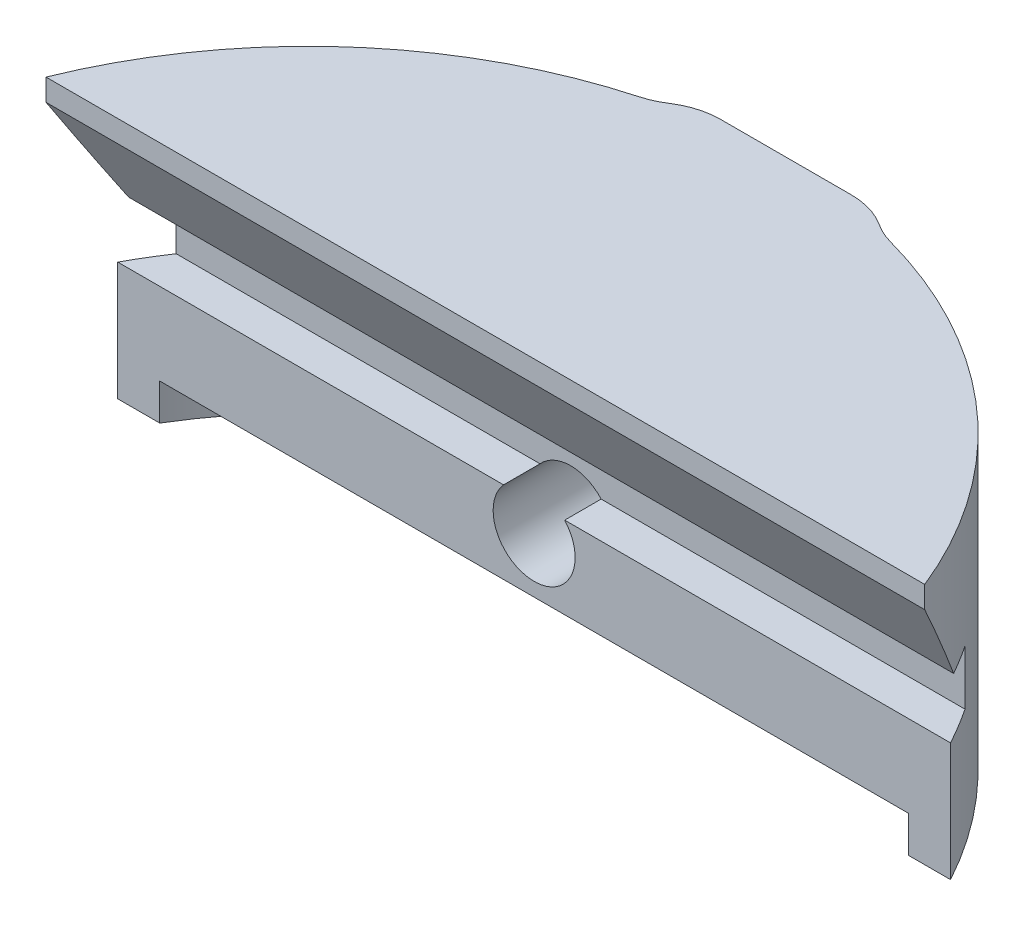
SolidWorks part; units mm, degrees
material "3.1355 (EN-AW 2024)"
ref_plane "Спереди" through (0, 0, 0) normal (0, 0, 1) x (1, 0, 0)
ref_plane "Сверху" through (0, 0, 0) normal (0, 1, 0) x (1, 0, 0)
ref_plane "Справа" through (0, 0, 0) normal (1, 0, 0) x (0, 0, -1)
sketch "Эскиз1" plane through (0, 0, 0) normal (0, 1, 0) x (1, 0, 0)
  circle A0 centre (0, 0) radius 26
  dimension "D1" = 52
extrude "Бобышка-Вытянуть1" add sketch "Эскиз1" along normal blind 14
sketch "Эскиз2" plane through (0, 0, 0) normal (1, 0, 0) x (0, 0, -1)
  line L0 (0, 14) -> (0, 0) construction
  line L1 (26, 14) -> (-26, 14) construction
  line L2 (13.6547, 6) -> (-13.6547, 6)
  line L3 (-13.6547, 6) -> (-9.7287, 12.8)
  line L4 (-9.7287, 12.8) -> (-9.7287, 14)
  line L5 (-9.7287, 14) -> (9.7287, 14)
  line L6 (0, 14) -> (0, 6) construction
  line L7 (13.6547, 6) -> (9.7287, 12.8)
  line L8 (9.7287, 12.8) -> (9.7287, 14)
  line L9 (-12.5, 8) -> (-12.5, 6) construction
  dimension "D1" = 8
  dimension "D2" = 1.2
  dimension "D3" = 60
  dimension "D4" = 13.6547
  dimension "D5" = 9.7287
  dimension "D6" = 2
  dimension "D7" = 12.5
extrude "Вырез-Вытянуть1" cut sketch "Эскиз2" against normal mid plane 60
sketch "Примерка" plane through (0, 0, 0) normal (1, 0, 0) x (0, 0, -1)
  line L0 (13.6547, 6) -> (-13.6547, 6) construction
  line L1 (-12.5, 14) -> (12.5, 14)
  line L2 (-12.5, 14) -> (-12.5, 6)
  line L3 (-12.5, 6) -> (12.5, 6)
  line L4 (12.5, 14) -> (12.5, 6)
  point P6 (0, 6)
  dimension "D1" = 8
  dimension "D2" = 25
sketch "Эскиз5" plane through (0, 0, 0) normal (0, -1, 0) x (1, 0, 0)
  line L2 (-22.1258, -15.6547) -> (22.1258, -15.6547)
  line L3 (-18.1915, -15.6547) -> (18.1915, -15.6547)
  circle A2 centre (0, 0) radius 24
  arc A3 (-18.1915, -15.6547) -> (18.1915, -15.6547) centre (0, 0) ccw
  dimension "D1" = 2
  dimension "D2" = 2
sketch "Эскиз6" plane through (0, 6, 0) normal (0, 1, 0) x (1, 0, 0)
  line L1 (18.4208, 0) -> (-15.4735, 0) construction
  circle A0 centre (0, 0) radius 6 construction
  circle A1 centre (0, 0) radius 12.5 construction
  dimension "D1" = 12
  dimension "D2" = 25
hole_wizard "Цековка для винта с внутренним шестигранником M32" positions "Эскиз14" profile "Эскиз13" counterbore size "M3" standard "Ansi Metric" end condition up to next
sketch "Эскиз14" plane through (0, 6, 0) normal (0, 1, 0) x (1, 0, 0)
  line L0 (18.4208, 0) -> (-15.4735, 0) construction
  circle A0 centre (0, 0) radius 12.5 construction
  circle A1 centre (0, 0) radius 6 construction
  point P0 (-12.5, 0)
  point P6 (12.5, 0)
  point P20 (-6, 0)
  point P24 (6, 0)
sketch "Эскиз13" plane through (-12.5, 6, 0) normal (1, 0, 0) x (0, 0, 1)
  line L0 (0, 0) -> (0, 6)
  line L1 (0, 6) -> (1.7, 6)
  line L3 (1.7, 6) -> (1.7, 3)
  line L4 (1.7, 3) -> (3.3, 3)
  line L5 (3.3, 3) -> (3.3, 0)
  line L7 (3.3, 0) -> (0, 0)
  line L11 (0, -6.35) -> (0, 107.95) construction
  dimension "Диаметр сквозного отверстия" = 3.4
  dimension "Глубина сквозного отверстия" = 6
  dimension "Диаметр цековки" = 6.6
  dimension "Глубина цековки" = 3
sketch "Эскиз12" plane through (0, 0, 0) normal (0, -1, 0) x (1, 0, 0)
  circle A0 centre (0, 0) radius 26 construction
  circle A1 centre (0, 0) radius 26
  circle A3 centre (0, 0) radius 24
  dimension "D1" = 2
extrude "Бобышка-Вытянуть2" add sketch "Эскиз12" along normal blind 2
sketch "Эскиз17" plane through (0, 14, 0) normal (0, 1, 0) x (1, 0, 0)
  line L0 (-24.1112, -9.7287) -> (24.1112, -9.7287) construction
  line L1 (-24.1112, -9.7287) -> (24.1112, -9.7287)
  arc A0 (-24.1112, -9.7287) -> (24.1112, -9.7287) centre (0, 0) ccw construction
  arc A1 (-24.1112, -9.7287) -> (24.1112, -9.7287) centre (0, 0) ccw
extrude "Вырез-Вытянуть4" cut sketch "Эскиз17" against normal up to surface (8 mm away) up to face at (9.25, 6, 0)
fillet "Скругление2" radius 1 4 edges at (9.25, 4.5, -0.5723) (9.25, 4.5, 0.5723) (-9.25, 4.5, 0.5723) (-9.25, 4.5, -0.5723)
sketch "Эскиз18" plane through (0, 0, 0) normal (0, -1, 0) x (1, 0, 0)
  circle A0 centre (0, 0) radius 6
extrude "Вырез-Вытянуть5" cut sketch "Эскиз18" against normal blind 3
sketch "Эскиз19" plane through (0, 6, 0) normal (0, 1, 0) x (1, 0, 0)
  line L0 (-22.3137, -13.3453) -> (22.3137, -13.3453)
  line L1 (-22.1258, 13.6547) -> (22.1258, 13.6547) construction
  arc A0 (-22.1258, 13.6547) -> (22.1258, 13.6547) centre (0, 0) ccw construction
  arc A1 (-22.3137, -13.3453) -> (22.3137, -13.3453) centre (0, 0) ccw
  dimension "D1" = 27
extrude "Вырез-Вытянуть6" cut sketch "Эскиз19" against normal blind 10
sketch "Эскиз21" plane through (0, 0, 13.3453) normal (0, 0, 1) x (1, 0, 0)
  line L0 (0, 0) -> (0, 6) construction
  line L1 (19.9475, 0) -> (-19.9475, 0) construction
  line L2 (22.3137, 6) -> (-22.3137, 6) construction
hole_wizard "Отверстие обработанное метчиком M4x0.71" positions "Эскиз23" profile "Эскиз22" tap size "M4x0.7" standard "Ansi Metric"
sketch "Эскиз23" plane through (0, 0, 13.3453) normal (0, 0, 1) x (1, 0, 0)
  line L0 (0, 0) -> (0, 6) construction
  point P0 (0, 3)
sketch "Эскиз22" plane through (0, 3, 13.3453) normal (1, 0, 0) x (0, -1, 0)
  line L0 (0, 0) -> (0, 12.4914)
  line L1 (0, 12.4914) -> (1.65, 11.5)
  line L2 (1.65, 11.5) -> (1.65, 0)
  line L5 (1.65, 0) -> (0, 0)
  line L10 (0, 12.4914) -> (-1.65, 11.5) construction
  line L11 (0, -6.35) -> (0, 107.95) construction
  dimension "Диаметр сверла" = 3.3
  dimension "Глубина сверла" = 11.5
  dimension "Угол заточки сверла" = 118
cosmetic thread "Отверстие резьбы1" parameters "D1"=8, "D2"=4
sketch "Эскиз20" plane through (0, 0, 13.3453) normal (0, 0, 1) x (1, 0, 0)
  line L0 (0, 3.1198) -> (0, -5.6063) construction
  line L1 (22.3137, 6) -> (-22.3137, 6) construction
  line L2 (-25.2658, 5) -> (25.2658, 5)
  line L3 (-25.2658, 5) -> (-25.2658, -2)
  line L4 (-25.2658, -2) -> (25.2658, -2)
  line L5 (25.2658, 5) -> (25.2658, -2)
  line L6 (-25.2658, 5) -> (25.2658, -2) construction
  line L7 (-25.2658, -2) -> (25.2658, 5) construction
  line L8 (-22.3137, -2) -> (-19.9475, -2) construction
  point P3 (0, 1.5)
  dimension "D1" = 1
extrude "Вырез-Вытянуть7" cut sketch "Эскиз20" against normal blind 2
sketch "Эскиз24" plane through (0, 0, 11.3453) normal (0, 0, 1) x (1, 0, 0)
  line L0 (0, 0) -> (0, -5.889) construction
  line L1 (-21.1491, 0) -> (21.1491, 0) construction
  line L2 (-11.3153, 1) -> (11.3153, 1)
  line L3 (-11.3153, 1) -> (-11.3153, 0)
  line L4 (-11.3153, 0) -> (11.3153, 0)
  line L5 (11.3153, 1) -> (11.3153, 0)
  line L6 (-11.3153, 1) -> (11.3153, 0) construction
  line L7 (-11.3153, 0) -> (11.3153, 1) construction
  point P3 (0, 0.5)
  dimension "D1" = 1
extrude "Бобышка-Вытянуть3" add sketch "Эскиз24" along normal blind 2
ref_plane "Плоскость1" through (26, 0, 0) normal (1, 0, 0) x (0, 0, -1)
sketch "Эскиз25" plane through (26, 0, 0) normal (1, 0, 0) x (0, 0, -1)
  line L0 (13.6547, 6) -> (13.6547, -5.3122) construction
  line L1 (12.4047, -5.3122) -> (-15.3444, -5.3122)
  line L2 (-15.3444, -5.3122) -> (-15.3444, 6)
  line L3 (-15.3444, 6) -> (12.4047, 6)
  line L4 (12.4047, 6) -> (12.4047, -5.3122)
  line L5 (13.6547, 6) -> (-13.3453, 6) construction
  dimension "D1" = 2.5
extrude "Вырез-Вытянуть8" cut sketch "Эскиз25" against normal through all
sketch "Эскиз26" plane through (26, 0, 0) normal (1, 0, 0) x (0, 0, -1)
  line L0 (12.4047, 7.5) -> (14.4047, 7.5)
  line L1 (14.4047, 7.5) -> (14.4047, 4.5)
  line L2 (14.4047, 4.5) -> (12.4047, 4.5)
  line L3 (12.4047, 4.5) -> (12.4047, 7.5)
  line L4 (12.4047, -2) -> (26, -2) construction
  line L7 (12.4047, 6) -> (12.4047, -2) construction
  dimension "D1" = 2
  dimension "D2" = 6.5
  dimension "D3" = 3
extrude "Вырез-Вытянуть10" cut sketch "Эскиз26" against normal through all
sketch "Эскиз27" plane through (0, 14, 0) normal (0, 1, 0) x (1, 0, 0)
  line L0 (0, 26) -> (0, 26.4574) construction
  line L2 (24.1112, 9.7287) -> (-24.1112, 9.7287) construction
  line L3 (-5, 26.2287) -> (5, 26.2287)
  line L4 (-5, 26.2287) -> (-5, 25.5147)
  line L6 (5, 26.2287) -> (5, 25.5147)
  line L7 (-5, 26.2287) -> (5.2086, 22.8067) construction
  line L8 (-6.2536, 22.4564) -> (5, 26.2287) construction
  arc A0 (-5, 25.5147) -> (5, 25.5147) centre (0, 0) cw
  arc A1 (24.1112, 9.7287) -> (-24.1112, 9.7287) centre (0, 0) ccw construction
  point P5 (0, 24.5527)
  point P18 (0, 26.2287)
  dimension "D1" = 10
  dimension "D2" = 16.5
extrude "Бобышка-Вытянуть5" add sketch "Эскиз27" against normal up to surface (16 mm away) up to face at (0, -2, -18.7024)
fillet "Скругление3" radius 4 2 edges at (5, 6, -25.5147) (-5, 6, -25.5147)
fillet "Скругление4" radius 4 2 edges at (5, 6, -26.2287) (-5, 6, -26.2287)
sketch "Эскиз28" plane through (0, 0, -26.2287) normal (0, 0, -1) x (-1, 0, 0)
  line L0 (0, -2) -> (0, 4.3259) construction
  line L1 (-3.5784, -2) -> (3.5784, -2) construction
  point P5 (0, 3)
  dimension "D1" = 5
hole_wizard "Отверстие с зазором M41" positions "Эскиз30" profile "Эскиз29" hole size "M4" standard "Ansi Metric" end condition through all
sketch "Эскиз30" plane through (0, 0, -26.2287) normal (0, 0, -1) x (-1, 0, 0)
  point P0 (0, 3)
sketch "Эскиз29" plane through (0, 3, -26.2287) normal (1, 0, 0) x (0, 1, 0)
  line L0 (0, 0) -> (0, 16.5)
  line L1 (0, 16.5) -> (2.25, 16.5)
  line L2 (2.25, 16.5) -> (2.25, 0)
  line L5 (2.25, 0) -> (0, 0)
  line L11 (0, -6.35) -> (0, 107.95) construction
  dimension "Диаметр сквозного отверстия" = 4.5
  dimension "Глубина сквозного отверстия" = 16.5
